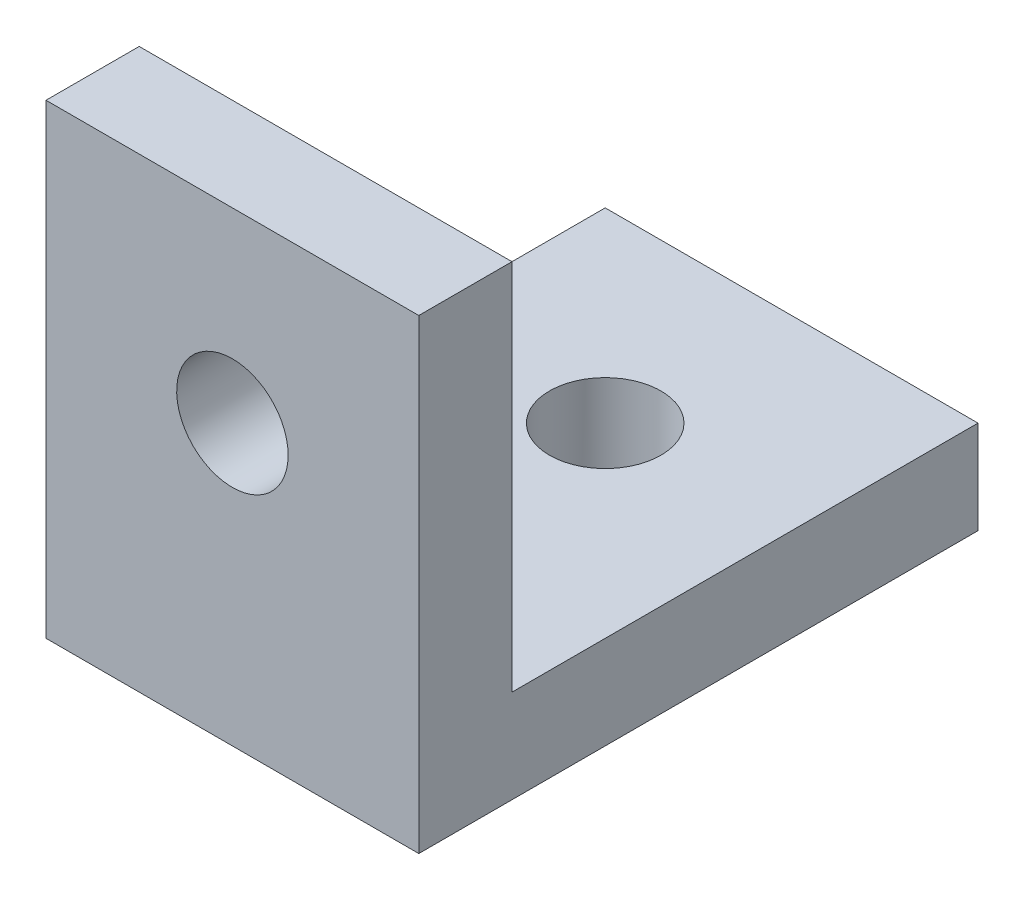
SolidWorks part; units mm, degrees
material "6061 Alloy"
ref_plane "Front Plane" through (0, 0, 0) normal (0, 0, 1) x (1, 0, 0)
ref_plane "Top Plane" through (0, 0, 0) normal (0, 1, 0) x (1, 0, 0)
ref_plane "Right Plane" through (0, 0, 0) normal (1, 0, 0) x (0, 0, -1)
sketch "Sketch2" plane through (0, 0, 0) normal (1, 0, 0) x (0, 0, -1)
  line L0 (0, 0) -> (0, 15.875)
  line L1 (0, 15.875) -> (3.175, 15.875)
  line L2 (3.175, 15.875) -> (3.175, 3.175)
  line L3 (3.175, 3.175) -> (19.05, 3.175)
  line L4 (19.05, 3.175) -> (19.05, 0)
  line L5 (19.05, 0) -> (0, 0)
  line L6 (0, 0) -> (0.1044, -0.0877)
  dimension "D1" = 19.05
  dimension "D2" = 15.875
  dimension "D3" = 3.175
  dimension "D4" = 3.175
extrude "Extrude1" add sketch "Sketch2" along normal blind 6.35 and the other way blind 6.35 contours L0 L1 L2 L3 L4 L5
hole_wizard "#6 Clearance Hole1" positions "3DSketch1" profile "Sketch3" hole size "#6" standard "Ansi Inch"
sketch3d "3DSketch1"
  line L0 (6.35, 15.875, -3.175) -> (-6.35, 15.875, -3.175) construction
  line L1 (6.35, 3.175, -19.05) -> (-6.35, 3.175, -19.05) construction
  line L3 (6.35, 15.875, -3.175) -> (6.35, 3.175, -3.175) construction
  line L6 (6.35, 3.175, -3.175) -> (6.35, 3.175, -19.05) construction
  point P0 (0, 9.525, -3.175)
  point P6 (0, 3.175, -12.7)
  dimension "D1" = 6.35
  dimension "D4" = 6.35
  dimension "D5" = 6.35
  dimension "D8" = 6.35
sketch "Sketch3" plane through (0, 9.525, -3.175) normal (1, 0, 0) x (0, 1, 0)
  line L0 (0, 0) -> (0, 13.8408)
  line L1 (0, 13.8408) -> (1.8986, 12.7)
  line L2 (1.8986, 12.7) -> (1.8986, 0)
  line L5 (1.8986, 0) -> (0, 0)
  line L10 (0, 13.8408) -> (-1.8987, 12.7) construction
  line L11 (0, -6.35) -> (0, 107.95) construction
  dimension "Hole Dia." = 3.7973
  dimension "Hole Depth" = 12.7
  dimension "Drill Angle" = 118
